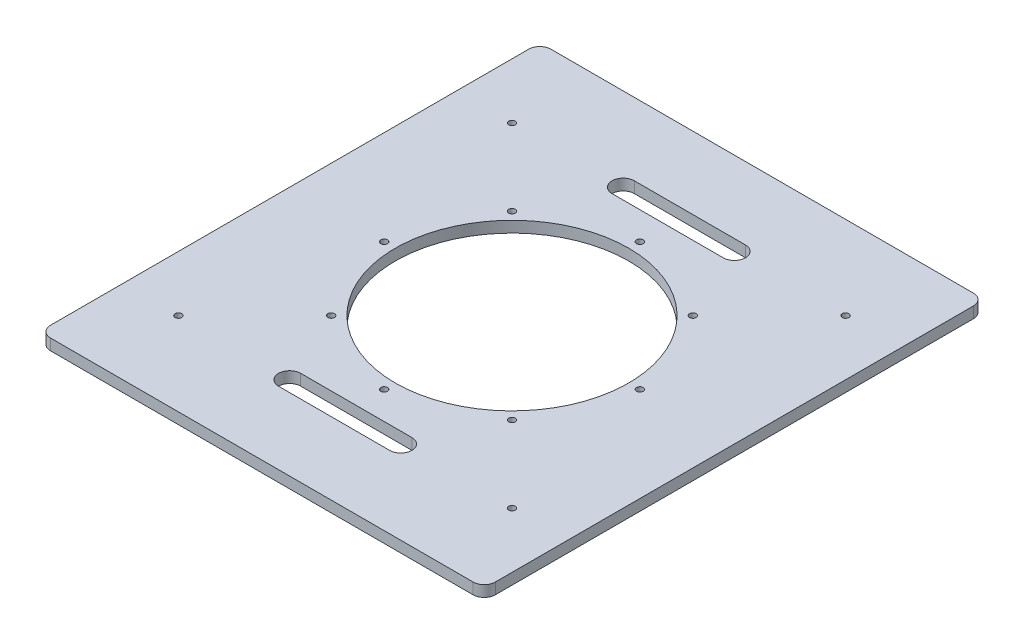
SolidWorks part; units mm, degrees
ref_plane "前基準面" through (0, 0, 0) normal (0, 0, 1) x (1, 0, 0)
ref_plane "上基準面" through (0, 0, 0) normal (0, 1, 0) x (1, 0, 0)
ref_plane "右基準面" through (0, 0, 0) normal (1, 0, 0) x (0, 0, -1)
sketch "草圖1" plane through (0, 0, 0) normal (0, 1, 0) x (1, 0, 0)
  line L0 (0, 250) -> (0, -250) construction
  line L1 (-250, 250) -> (250, 250) construction
  line L2 (-250, 250) -> (-250, -250) construction
  line L3 (-250, -250) -> (250, -250) construction
  line L4 (250, 250) -> (250, -250) construction
  line L5 (-200, 215) -> (-200, -215)
  line L6 (-200, 0) -> (200, 0) construction
  line L7 (-190, 225) -> (190, 225)
  line L9 (-190, -225) -> (190, -225)
  line L11 (0, -225) -> (0, 225) construction
  line L12 (-200, 0) -> (200, 0) construction
  line L31 (200, 215) -> (200, -215)
  arc A0 (200, 215) -> (190, 225) centre (190, 215) ccw
  arc A1 (-190, 225) -> (-200, 215) centre (-190, 215) ccw
  arc A2 (190, -225) -> (200, -215) centre (190, -215) ccw
  arc A3 (-200, -215) -> (-190, -225) centre (-190, -215) ccw
  point P0 (0, 0)
  point P8 (0, 0)
  point P11 (0, 0)
  point P38 (200, 225)
  point P41 (-200, 225)
  point P44 (200, -225)
  dimension "D9" = 10
  dimension "D1" = 500
  dimension "D2" = 500
  dimension "D3" = 400
  dimension "D4" = 450
extrude "填料-伸長1" add sketch "草圖1" along normal blind 10
sketch "草圖3" plane through (0, 10, 0) normal (0, 1, 0) x (1, 0, 0)
  line L0 (0, 240.0553) -> (0, -270.0297) construction
  line L1 (-314.6258, 0) -> (222.5458, 0) construction
  line L8 (-150, 150) -> (150, 150) construction
  line L9 (165, -165) -> (135, -165) construction
  line L12 (-150, 150) -> (-150, -150) construction
  line L13 (-165, -135) -> (-135, -135) construction
  line L22 (-150, -150) -> (150, -150) construction
  line L23 (150, 150) -> (150, -150) construction
  line L24 (-165, -135) -> (-165, -165) construction
  line L25 (-165, -165) -> (-135, -165) construction
  line L26 (-135, -135) -> (-135, -165) construction
  line L27 (-150, -165) -> (-150, -135) construction
  line L28 (-165, -150) -> (-135, -150) construction
  line L29 (135, -135) -> (135, -165) construction
  line L30 (165, -135) -> (135, -135) construction
  line L31 (165, -135) -> (165, -165) construction
  line L32 (-165, 165) -> (-135, 165) construction
  line L33 (-135, 135) -> (-135, 165) construction
  line L34 (-165, 135) -> (-135, 135) construction
  line L35 (-165, 135) -> (-165, 165) construction
  line L36 (165, 135) -> (165, 165) construction
  line L37 (165, 135) -> (135, 135) construction
  line L38 (135, 135) -> (135, 165) construction
  line L39 (165, 165) -> (135, 165) construction
  line L40 (-50, -150) -> (50, -150) construction
  line L41 (-50, -140) -> (50, -140)
  line L42 (-50, -160) -> (50, -160)
  line L43 (-50, 150) -> (50, 150) construction
  line L44 (-50, 140) -> (50, 140)
  line L45 (-50, 160) -> (50, 160)
  circle A0 centre (0, 0) radius 125 construction
  circle A1 centre (0, 0) radius 105
  circle A2 centre (0, 115) radius 3
  circle A3 centre (81.3173, 81.3173) radius 3
  circle A4 centre (115, 0) radius 3
  circle A5 centre (81.3173, -81.3173) radius 3
  circle A6 centre (0, -115) radius 3
  circle A7 centre (-81.3173, -81.3173) radius 3
  circle A8 centre (-115, 0) radius 3
  circle A9 centre (-81.3173, 81.3173) radius 3
  circle A10 centre (-150, 150) radius 3
  circle A12 centre (150, 150) radius 3
  circle A13 centre (-150, -150) radius 3
  circle A14 centre (150, -150) radius 3
  arc A15 (-50, -140) -> (-50, -160) centre (-50, -150) ccw
  arc A16 (50, -160) -> (50, -140) centre (50, -150) ccw
  arc A17 (-50, 140) -> (-50, 160) centre (-50, 150) cw
  arc A18 (50, 160) -> (50, 140) centre (50, 150) cw
  point P5 (150, 0)
  point P28 (0, 0)
  point P31 (0, -150)
  point P56 (0, -150)
  point P61 (0, -150)
  point P62 (0, -150)
  point P65 (0, 150)
  point P70 (0, 0)
  dimension "D1" = 250
  dimension "D3" = 6
  dimension "D4" = 115
  dimension "D11" = 10
  dimension "D10" = 6
  dimension "D6" = 300
  dimension "D7" = 300
  dimension "D8" = 30
  dimension "D9" = 30
  dimension "D12" = 100
  dimension "D2" = 20
  dimension "D5" = 8
extrude "除料-伸長1" cut sketch "草圖3" against normal blind 15
